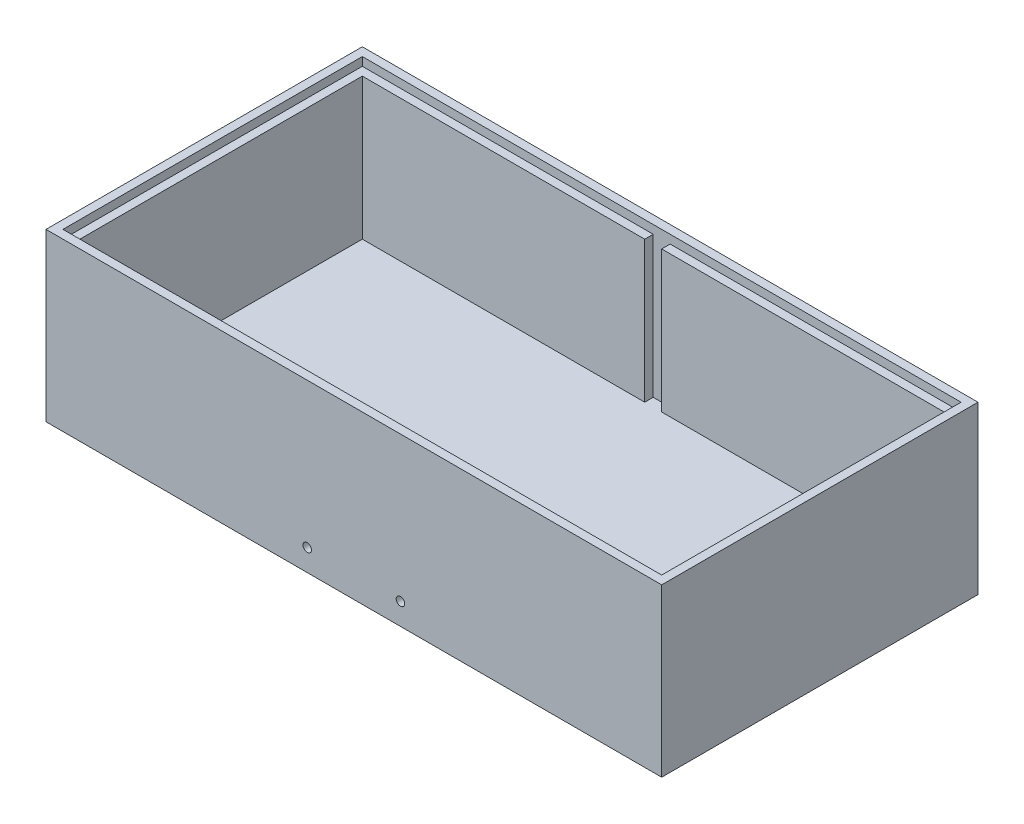
SolidWorks part; units mm, degrees
ref_plane "Front Plane" through (0, 0, 0) normal (0, 0, 1) x (1, 0, 0)
ref_plane "Top Plane" through (0, 0, 0) normal (0, 1, 0) x (1, 0, 0)
ref_plane "Right Plane" through (0, 0, 0) normal (1, 0, 0) x (0, 0, -1)
sketch "Sketch1" plane through (0, 0, 0) normal (0, 1, 0) x (1, 0, 0)
  line L1 (0, -56) -> (-109, -56)
  line L2 (0, -56) -> (0, 56)
  line L3 (0, 56) -> (-109, 56)
  line L4 (-109, -56) -> (-109, 56)
  point P4 (0, 0)
  dimension "D1" = 109
  dimension "D2" = 112
extrude "Boss-Extrude1" add sketch "Sketch1" along normal blind 59 contours L1 L4 L3 L2
sketch "Sketch2" plane through (0, 59, 0) normal (0, 1, 0) x (1, 0, 0)
  line L0 (-109, -56) -> (-109, 56) construction
  line L1 (-103, 50) -> (-6, 50)
  line L2 (-103, 50) -> (-103, -50)
  line L3 (-103, -50) -> (-6, -50)
  line L4 (-6, 50) -> (-6, -50)
  line L5 (-103, 0) -> (-109, 0)
  line L6 (0, 56) -> (-109, 56) construction
  line L7 (-54.5, 50) -> (-54.5, 56)
  line L8 (-6, 0) -> (0, 0)
  line L9 (-103, 50) -> (-106, 50)
  line L10 (-106, 53) -> (-3, 53)
  line L11 (-106, 53) -> (-106, -53)
  line L12 (-106, -53) -> (-3, -53)
  line L13 (-3, 53) -> (-3, -53)
  line L14 (-103, 53) -> (-103, 50)
  line L15 (-6, -50) -> (-6, -53)
  line L16 (-6, -50) -> (-3, -50)
  line L17 (-3, 53) -> (0, 53)
  line L18 (0, -56) -> (0, 56) construction
  line L19 (-3, -53) -> (0, -53)
  line L20 (-6, 50) -> (-3, 50)
  line M5 (0, -56) -> (0, 56)
  dimension "D1" = 6
  dimension "D2" = 3
extrude "Cut-Extrude1" cut sketch "Sketch2" against normal blind 53 contours L4 L1 L2 L3 | L13 L19 L8 M5 | L17 L13 L8 M5 | L4 L16 L13 L8 | L20 L4 L8 L13 region at (-54.5, 59, 0) region at (-4.5, 59, -25) region at (-4.5, 59, 25) region at (-1.5, 59, -26.5) region at (-1.5, 59, 26.5)
extrude "Cut-Extrude2" cut sketch "Sketch2<3>" against normal blind 3 contours L15 L3 L2 L5 L11 L12 | L4 L16 L13 L8 | L13 L10 L7 L1 L4 L8 | L10 L14 L1 L7 | L9 L11 L5 L2 | L14 L10 L11 L9 | L16 L15 L12 L13 region at (-78.75, 59, -51.5) region at (-104.5, 59, -25) region at (-104.5, 59, -51.5) region at (-28.75, 59, -51.5) region at (-104.1318, 59, 25) region at (-4.5, 59, 25) region at (-4.5, 59, 51.5)
sketch "Sketch2<3>" plane through (0, 59, 0) normal (0, 1, 0) x (1, 0, 0) same geometry as "Sketch2"
sketch "Sketch6" plane through (0, 0, 56) normal (0, 0, 1) x (1, 0, 0)
  line L0 (0, 0) -> (-109, 0) construction
  circle A0 centre (-16.5, 7.7) radius 1.5
  point P6 (-15, 7.7)
  point P8 (-18, 7.7)
  dimension "D1" = 3
  dimension "D2" = 7.7
  dimension "D3" = 18
extrude "Cut-Extrude28" cut sketch "Sketch6" against normal blind 6
mirror "Mirror1" about plane through (0, 0, 0) normal (1, 0, 0) of "Boss-Extrude1", "Cut-Extrude28", "Cut-Extrude1", "Cut-Extrude2"
equation "\"RoomSize\"= 100mm"
equation "\"D1@Sketch1\"= \"RoomSize\" + ( 3 / 2 ) * \"WallsThick\""
equation "\"WallsThick\"= 6mm"
equation "\"D1@Boss-Extrude1\"=\"RoomHeight\"+\"WallsThick\"+\"CoverThick\""
equation "\"D1@Sketch2\"=\"WallsThick\""
equation "\"D1@Cut-Extrude1\"=\"RoomHeight\"+\"CoverThick\""
equation "\"D2@Sketch2\"=\"WallsThick\"/2"
equation "\"CoverThick\"= \"WallsThick\"/2"
equation "\"D1@Cut-Extrude2\"=\"CoverThick\""
equation "\"ShieldHeight\"= 4mm"
equation "\"ShieldLength\"= \"ModelLength\"/2"
equation "\"ShieldThick\"= 1mm"
equation "\"MeasureHoleSize\"= 3mm"
equation "\"D1\"= \"WallsThick\" + \"CoverHolderSize\""
equation "\"D1@Sketch6\"=\"MeasureHoleSize\""
equation "\"D2@Sketch6\"=\"WallsThick\"+\"ModelHeight\""
equation "\"D3@Sketch6\"=\"ModelLength\" / 2 + \"WallsThick\" / 2"
equation "\"ModelHeight\"= 1.7mm"
equation "\"RoomHeight\"= 5cm"
equation "\"HoleHeight\"= 3mm"
equation "\"HoleWidth\"= 13mm"
equation "\"HoleOffSet\"= 0"
equation "\"D2@Sketch1\"=\"RoomSize\"+2*\"WallsThick\""
equation "\"D1@Cut-Extrude28\"=\"WallsThick\""
equation "\"ModelLength\"= 30mm"
